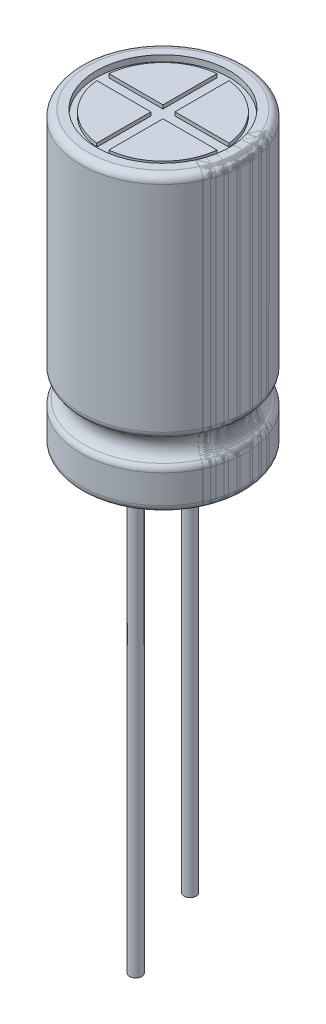
SolidWorks part; units mm, degrees
note: The reader was unsure of these and kept them because the rebuilt part matched: shared geometry of "Sketch7<4>".
ref_plane "Front Plane" through (0, 0, 0) normal (0, 0, 1) x (1, 0, 0)
ref_plane "Top Plane" through (0, 0, 0) normal (0, 1, 0) x (1, 0, 0)
ref_plane "Right Plane" through (0, 0, 0) normal (1, 0, 0) x (0, 0, -1)
sketch "Sketch1" plane through (0, 0, 0) normal (0, 0, 1) x (1, 0, 0)
  line L8 (0, 0.6) -> (2.8, 0.6)
  line L9 (2.8, 0.6) -> (2.8, 0.4)
  line L10 (2.8, 0.4) -> (3.1, 0.4)
  line L11 (3.4, 0.7) -> (3.4, 1.8735)
  line L12 (3.1, 12.5) -> (2.75, 12.5)
  line L13 (2.75, 12.5) -> (2.75, 12.25)
  line L14 (2.75, 12.25) -> (0, 12.25)
  line L15 (0, 12.25) -> (0, 0.6)
  line L16 (1.2518, 2.6) -> (5.492, 2.6) construction
  line L17 (3.4, 3.3265) -> (3.4, 12.2)
  arc A0 (3.1, 0.4) -> (3.4, 0.7) centre (3.1, 0.7) ccw
  arc A1 (3.4, 12.2) -> (3.1, 12.5) centre (3.1, 12.2) ccw
  arc A2 (3.2701, 3.0794) -> (3.2701, 2.1206) centre (3.6, 2.6) ccw
  arc A3 (3.4, 1.8735) -> (3.2701, 2.1206) centre (3.1, 1.8735) ccw
  arc A4 (3.4, 3.3265) -> (3.2701, 3.0794) centre (3.1, 3.3265) cw
  dimension "D8" = 0.3
  dimension "D11" = 1.1639
  dimension "D12" = 0.3
  dimension "D1" = 11.65
  dimension "D2" = 0.2
  dimension "D3" = 0.6
  dimension "D4" = 2.75
  dimension "D5" = 0.65
  dimension "D6" = 0.25
  dimension "D7" = 0.6
  dimension "D9" = 2.2
  dimension "D10" = 3.6
revolve "Revolve1" add sketch "Sketch1" angle 360 about L15
sketch "Sketch2" plane through (0, 12.25, 0) normal (0, 1, 0) x (1, 0, 0)
  line L0 (-0.25, 0.25) -> (-0.25, 2.4875)
  line L2 (0.25, -2.4875) -> (0.25, -0.25)
  line L4 (-0.25, -2.4875) -> (-0.25, -0.25)
  line L5 (0.25, 0.25) -> (0.25, 2.4875)
  line L7 (2.4875, -0.25) -> (0.25, -0.25)
  line L9 (2.4875, 0.25) -> (0.25, 0.25)
  line L13 (-0.25, -0.25) -> (-2.4875, -0.25)
  line L16 (-0.25, 0.25) -> (-2.4875, 0.25)
  arc A0 (0.25, -2.4875) -> (2.4875, -0.25) centre (0, 0) ccw
  arc A1 (2.4875, 0.25) -> (0.25, 2.4875) centre (0, 0) ccw
  arc A2 (-0.25, 2.4875) -> (-2.4875, 0.25) centre (0, 0) ccw
  arc A3 (-2.4875, -0.25) -> (-0.25, -2.4875) centre (0, 0) ccw
  dimension "D3" = 2.5
  dimension "D1" = 0.5
  dimension "D2" = 0.5
extrude "Boss-Extrude1" add sketch "Sketch2" along normal blind 0.15 separate body
sketch "Sketch3" plane through (0, 0.6, 0) normal (0, -1, 0) x (1, 0, 0)
  circle A0 centre (0, 0) radius 1.8
  ellipse E0 centre (0, 0) end of major axis (-1.67, 0) minor radius 0.9
  dimension "D1" = 3.6
extrude "Boss-Extrude2" add sketch "Sketch3" along normal blind 0.6 separate body
sketch "Sketch4" plane through (0, 0.6, 0) normal (0, -1, 0) x (1, 0, 0)
sketch "Sketch5" plane through (0, 0, 0) normal (0, 0, 1) x (1, 0, 0)
  line L8 (2.75, 12.5) -> (3.1, 12.5)
  line L10 (3.4, 3.3265) -> (3.4, 12.2) construction
  line L11 (3.4, 12.2) -> (3.4, 3.3265)
  line L12 (2.75, 12.5) -> (2.8, 0.4)
  line L13 (2.8, 0.4) -> (3.1, 0.4)
  line L14 (0, 0) -> (0, 15.0032) construction
  line L16 (3.4, 0.7) -> (3.4, 1.8735)
  arc A5 (3.1, 12.5) -> (3.4, 12.2) centre (3.1, 12.2) cw
  arc A6 (3.1, 0.4) -> (3.4, 0.7) centre (3.1, 0.7) ccw construction
  arc A7 (3.4, 1.8735) -> (3.2701, 2.1206) centre (3.1, 1.8735) ccw
  arc A8 (3.4, 3.3265) -> (3.2701, 3.0794) centre (3.1, 3.3265) cw
  arc A9 (3.2701, 3.0794) -> (3.2701, 2.1206) centre (3.6, 2.6) ccw
  arc A10 (3.4, 0.7) -> (3.1, 0.4) centre (3.1, 0.7) cw
revolve "Revolve3" add sketch "Sketch5" angle 25 about L14
sketch "Sketch7" plane through (0, 0.6, 0) normal (0, -1, 0) x (1, 0, 0)
  line L0 (-1.4523, 0) -> (1.4342, 0) construction
  line L1 (0, 0) -> (0, 0.7626) construction
  circle A0 centre (-1.125, 0) radius 0.25
  circle A2 centre (1.125, 0) radius 0.25
  dimension "D2" = 0.5
  dimension "D1" = 1.125
extrude "Boss-Extrude3" add sketch "Sketch7" along normal blind 19.6 contours A0
extrude "Boss-Extrude4" add sketch "Sketch7<4>" along normal blind 15.6 contours A2
sketch "Sketch7<4>" plane through (0, 0.6, 0) normal (0, -1, 0) x (1, 0, 0) same geometry as "Sketch7"
